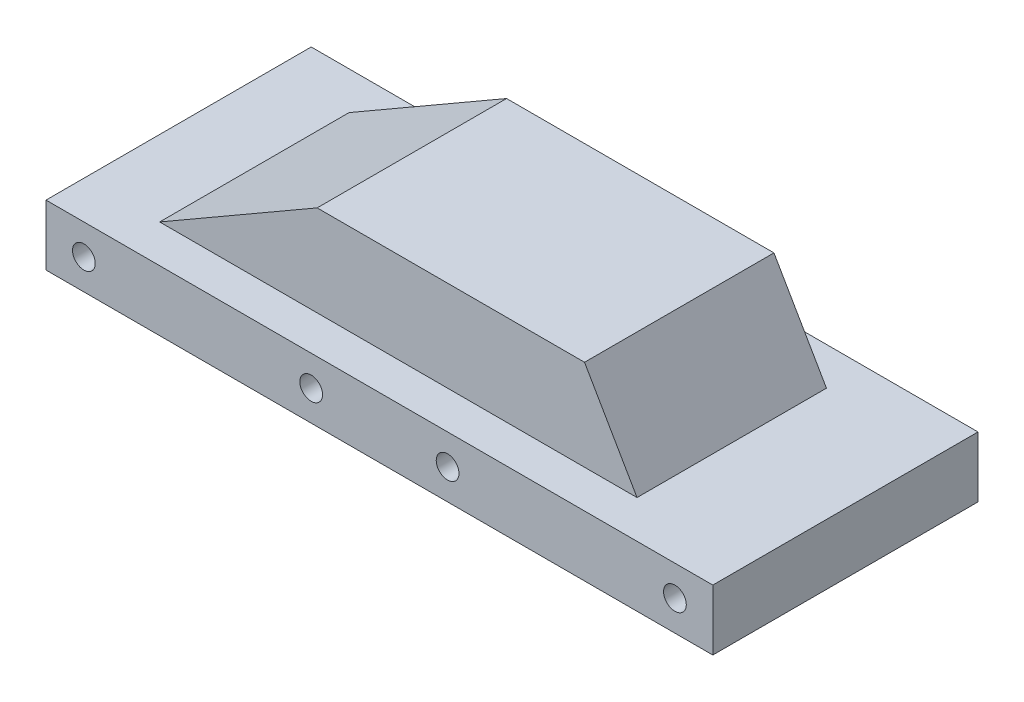
SolidWorks part; units mm, degrees
ref_plane "前视基准面" through (0, 0, 0) normal (0, 0, 1) x (1, 0, 0)
ref_plane "上视基准面" through (0, 0, 0) normal (0, 1, 0) x (1, 0, 0)
ref_plane "右视基准面" through (0, 0, 0) normal (1, 0, 0) x (0, 0, -1)
sketch "草图1" plane through (0, 0, 0) normal (0, 1, 0) x (1, 0, 0)
  line L1 (-44, -17.5) -> (44, -17.5)
  line L2 (-44, -17.5) -> (-44, 17.5)
  line L3 (-44, 17.5) -> (44, 17.5)
  line L4 (44, -17.5) -> (44, 17.5)
  line L5 (-44, -17.5) -> (44, 17.5) construction
  line L6 (-44, 17.5) -> (44, -17.5) construction
  point P0 (0, 0)
  dimension "D1" = 88
  dimension "D2" = 35
extrude "凸台-拉伸1" add sketch "草图1" along normal blind 4 and the other way blind 4
sketch "草图2" plane through (0, 0, -17.5) normal (0, 0, -1) x (-1, 0, 0)
  circle A0 centre (39, 0) radius 1.5
  circle A1 centre (-39, 0) radius 1.5
  circle A2 centre (-9, 0) radius 1.5
  circle A3 centre (9, 0) radius 1.5
  dimension "D1" = 9
  dimension "D2" = 39
  dimension "D3" = 9
  dimension "D4" = 39
extrude "切除-拉伸1" cut sketch "草图2" against normal through all
sketch "草图3" plane through (0, 0, 0) normal (0, 0, 1) x (1, 0, 0)
  line L0 (29, 4) -> (22.0718, 16)
  line L1 (44, 4) -> (-44, 4) construction
  line L2 (22.0718, 16) -> (-13.2154, 16)
  line L3 (-13.2154, 16) -> (-34, 4)
  line L4 (-34, 4) -> (29, 4)
  dimension "D1" = 120
  dimension "D2" = 150
  dimension "D3" = 12
  dimension "D4" = 10
  dimension "D5" = 15
extrude "凸台-拉伸2" add sketch "草图3" along normal mid plane 25
